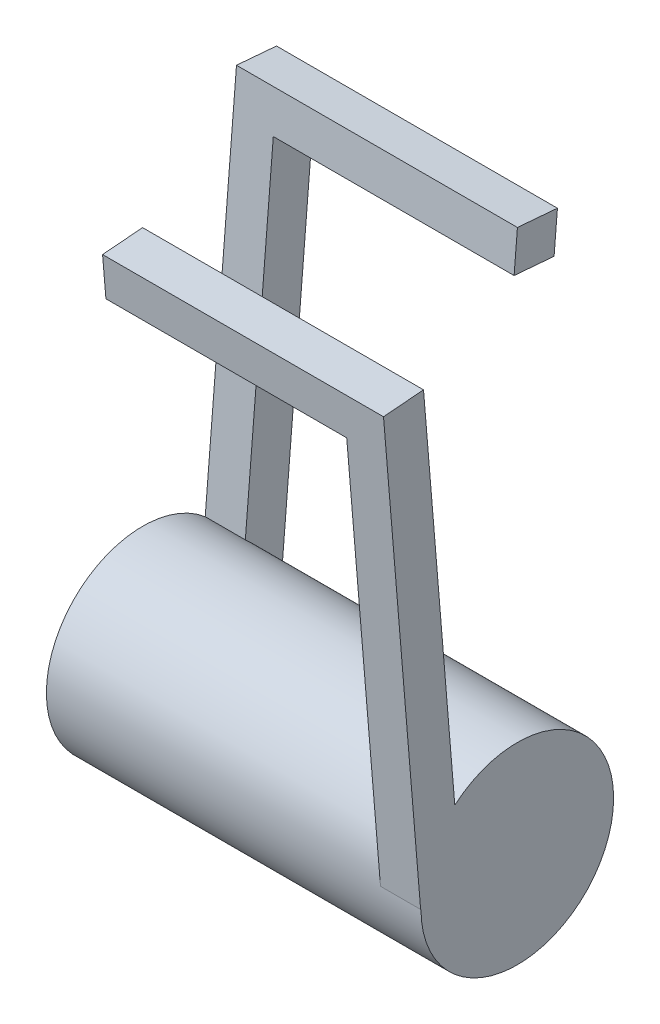
SolidWorks part; units mm, degrees
ref_plane "Front Plane" through (0, 0, 0) normal (0, 0, 1) x (1, 0, 0)
ref_plane "Top Plane" through (0, 0, 0) normal (0, 1, 0) x (1, 0, 0)
ref_plane "Right Plane" through (0, 0, 0) normal (1, 0, 0) x (0, 0, -1)
sketch "Sketch1" plane through (0, 0, 0) normal (1, 0, 0) x (0, 0, -1)
  circle A0 centre (0, 0) radius 3.6
  dimension "D1" = 7.2
extrude "Boss-Extrude1" add sketch "Sketch1" along normal blind 14
sketch "Sketch2" plane through (0, 0, 0) normal (-1, 0, 0) x (0, 0, 1)
  line L1 (-5, 16.6423) -> (-3.5052, 16.7669)
  line L2 (-5, 16.6423) -> (-3.6125, 0)
  line L3 (-3.6125, 0) -> (-2.1177, 0.1246)
  line L4 (-3.5052, 16.7669) -> (-2.1177, 0.1246)
  circle A0 centre (0, 0) radius 3.6 construction
  point P6 (0, 0)
  point P8 (0, 0)
  point P9 (-4.415, 16.7531)
  dimension "D1" = 1.5
  dimension "D2" = 16.7
  dimension "D3" = 5
extrude "Boss-Extrude2" add sketch "Sketch2" against normal blind 1.5
sketch "Sketch4" plane through (1.5, 0, 0) normal (1, 0, 0) x (0, 0, -1)
  line L0 (2.3357, 2.7395) -> (3.5052, 16.7669) construction
  line L1 (5, 16.6423) -> (3.5052, 16.7669)
  line L2 (5, 16.6423) -> (4.8754, 15.1474)
  line L3 (4.8754, 15.1474) -> (3.3806, 15.2721)
  line L4 (3.5052, 16.7669) -> (3.3806, 15.2721)
  line L5 (3.5052, 16.7669) -> (5, 16.6423) construction
  dimension "D1" = 1.5
extrude "Boss-Extrude3" add sketch "Sketch4" along normal blind 9 contours L2 L1 L4 L3
ref_plane "Plane1" through (7, 0, 0) normal (-1, 0, 0) x (0, 0, 1)
ref_axis "Axis1" through (7, 17.7852, 0) along (0, -1, 0)
pattern_circular "CirPattern1" count 2 every 180 about axis through (7, 17.7852, 0) along (0, -1, 0) of "Boss-Extrude2", "Boss-Extrude3"
